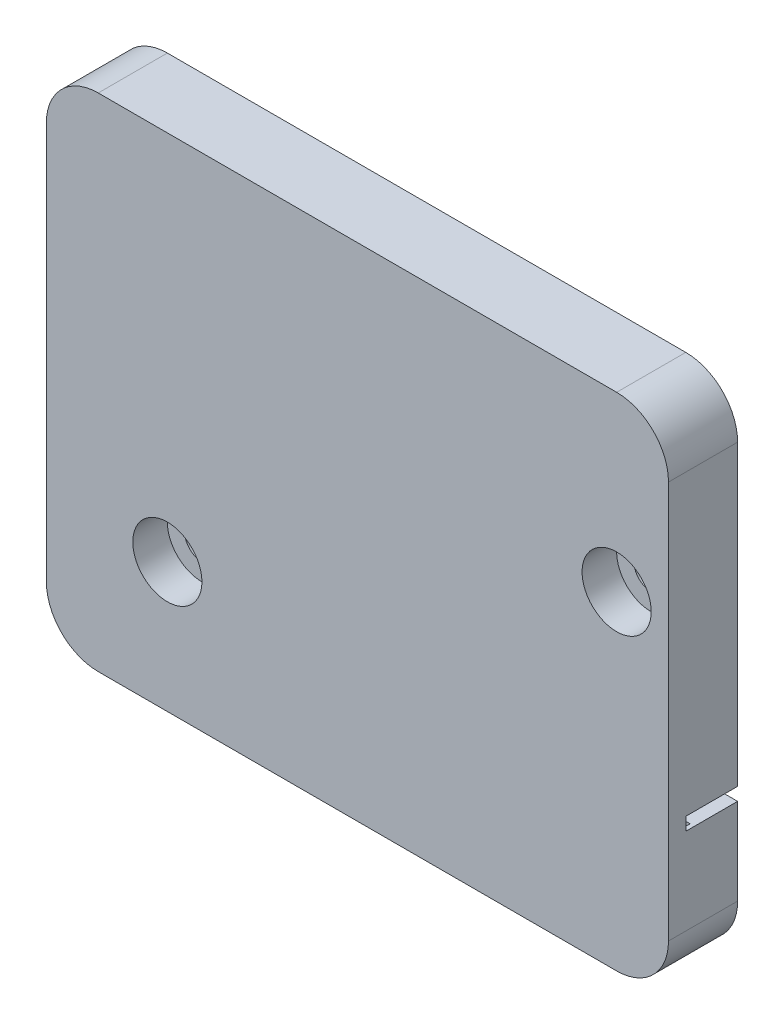
SolidWorks part; units mm, degrees
ref_plane "Front Plane" through (0, 0, 0) normal (0, 0, 1) x (1, 0, 0)
ref_plane "Top Plane" through (0, 0, 0) normal (0, 1, 0) x (1, 0, 0)
ref_plane "Right Plane" through (0, 0, 0) normal (1, 0, 0) x (0, 0, -1)
sketch "Sketch1" plane through (0, 0, 0) normal (0, 0, 1) x (1, 0, 0)
  line L0 (36, 29) -> (-36, -29) construction
  line L1 (-36, -29) -> (36, -29)
  line L2 (-36, -29) -> (-36, 23)
  line L3 (-30, 29) -> (30, 29)
  line L4 (36, -29) -> (36, 23)
  arc A0 (30, 29) -> (36, 23) centre (30, 23) cw
  arc A1 (-36, 23) -> (-30, 29) centre (-30, 23) cw
  dimension "D1" = 6
  dimension "D2" = 72
  dimension "D3" = 58
extrude "Boss-Extrude1" add sketch "Sketch1" along normal blind 8
sketch "Sketch2" plane through (0, 0, 0) normal (0, 0, -1) x (-1, 0, 0)
  line L0 (-33, 0.927) -> (18.4072, 26)
  line L1 (18.4072, 26) -> (30, 26)
  line L2 (33, 23) -> (33, 4.1897)
  line L3 (33, 4.1897) -> (-36, -29.4638)
  line L4 (-33, -9.5) -> (-33, 0.927)
  line L5 (-26.4193, 4.1366) -> (6, 19.9486) construction
  line L6 (36, 5.6529) -> (-15.0217, -19.232) construction
  line L7 (36, 23) -> (36, -29) construction
  line L8 (-30, 29) -> (30, 29) construction
  line L10 (-36, -29) -> (-36, 23) construction
  line L11 (-35, -11.5) -> (-36, -11.5)
  line L12 (-36, -11.5) -> (-36, -29.4638)
  arc A0 (30, 26) -> (33, 23) centre (30, 23) cw
  arc A1 (-35, -11.5) -> (-33, -9.5) centre (-35, -9.5) ccw
  dimension "D3" = 3
  dimension "D6" = 2
  dimension "D1" = 3
  dimension "D2" = 3
  dimension "D4" = 3
  dimension "D5" = 17.9638
extrude "Cut-Extrude1" cut sketch "Sketch2" against normal blind 6
sketch "Sketch3" plane through (0, 0, 8) normal (0, 0, 1) x (1, 0, 0)
  circle A0 centre (-22, -14) radius 2
  circle A1 centre (30, 9) radius 2
  dimension "D1" = 4
extrude "Cut-Extrude2" cut sketch "Sketch3" against normal through all
sketch "Sketch4" plane through (0, 0, 8) normal (0, 0, 1) x (1, 0, 0)
  circle A0 centre (-22, -14) radius 4
  circle A1 centre (30, 9) radius 4
  dimension "D1" = 8
extrude "Cut-Extrude3" cut sketch "Sketch4" against normal blind 4
fillet "Fillet2" radius 6 2 edges at (36, -29, 7) (-36, -29, 4)
fillet "Fillet1" radius 2 1 edges at (33.1796, -28.0882, 3)
sketch "Sketch6" plane through (0, 0, 6) normal (0, 0, -1) x (-1, 0, 0)
  line L0 (-36, -11.5) -> (-36, -23) construction
  line L1 (-26.3861, -29) -> (-30, -29) construction
  line L2 (-36, -13) -> (-36, -23)
  line L3 (-29.3861, -29) -> (-30, -29)
  line L4 (-36, -13) -> (-35.5, -13)
  line L5 (-35.5, -13) -> (-35.5, -23)
  line L6 (-30, -28.5) -> (-29.3861, -28.5)
  line L7 (-29.3861, -28.5) -> (-29.3861, -29)
  line L8 (-31, -4.9122) -> (28.2788, 24)
  line L9 (28.2788, 24) -> (28.498, 23.5506)
  line L10 (28.498, 23.5506) -> (-30.7808, -5.3616)
  line L11 (-30.7808, -5.3616) -> (-31, -4.9122)
  line L12 (-33.5, -13.5025) -> (30.7808, 17.8493)
  line L13 (30.7808, 17.8493) -> (31, 17.3999)
  line L14 (31, 17.3999) -> (-33.2808, -13.9519)
  line L15 (-33.2808, -13.9519) -> (-33.5, -13.5025)
  line L16 (-33.5, -20.8735) -> (30.7808, 10.4783)
  line L17 (30.7808, 10.4783) -> (31, 10.0289)
  line L18 (31, 10.0289) -> (-33.2808, -21.3229)
  line L19 (-33.2808, -21.3229) -> (-33.5, -20.8735)
  line L20 (18.4072, 26) -> (-33, 0.927) construction
  line L23 (30, 26) -> (18.4072, 26) construction
  line L24 (-33, 0.927) -> (-33, -9.5) construction
  line L25 (33, 4.1897) -> (33, 23) construction
  line L26 (33, 4.1897) -> (33, 23) construction
  line L27 (-10.2244, 5.2208) -> (-12.9094, 10.7259) construction
  line L28 (18.4072, 26) -> (-33, 0.927) construction
  line L29 (-8.4412, 5.5341) -> (-5.7562, 0.029) construction
  line L30 (-6.2562, -0.7711) -> (-3.5712, -6.2763) construction
  line L31 (-3.5712, -6.8326) -> (-0.8862, -12.3377) construction
  line L32 (-27.2628, -25.2024) -> (33, 4.1897) construction
  arc A0 (-36, -23) -> (-30, -29) centre (-30, -23) ccw construction
  arc A1 (-36, -23) -> (-30, -29) centre (-30, -23) ccw
  arc A2 (-35.5, -23) -> (-30, -28.5) centre (-30, -23) ccw
  dimension "D1" = 0.5
  dimension "D2" = 1.5
  dimension "D3" = 3
  dimension "D4" = 2
  dimension "D5" = 2
  dimension "D6" = 2
  dimension "D7" = 2
  dimension "D8" = 2
  dimension "D9" = 2
extrude "Boss-Extrude3" add sketch "Sketch6" along normal blind 1
sketch "Sketch7" plane through (0, 0, 5) normal (0, 0, -1) x (-1, 0, 0)
  line L0 (30.7808, 10.4783) -> (-33.5, -20.8735) construction
  line L1 (30.7808, 17.8493) -> (-33.5, -13.5025) construction
  line L2 (28.2788, 24) -> (-31, -4.9122) construction
  line L3 (-36, -13) -> (-36, -23) construction
  line L4 (-30, -29) -> (-29.3861, -29) construction
  line L5 (30.7808, 10.4783) -> (-33.5, -20.8735)
  line L6 (30.7808, 17.8493) -> (-33.5, -13.5025)
  line L7 (28.2788, 24) -> (-31, -4.9122)
  line L8 (-36, -13) -> (-36, -23)
  line L9 (-30, -29) -> (-29.3861, -29)
  line L10 (-31, -4.9122) -> (-30.1233, -6.7098)
  line L11 (-30.1233, -6.7098) -> (29.1555, 22.2024)
  line L12 (29.1555, 22.2024) -> (28.2788, 24)
  line L13 (30.7808, 17.8493) -> (31.6576, 16.0517)
  line L14 (31.6576, 16.0517) -> (-32.6233, -15.3001)
  line L15 (-32.6233, -15.3001) -> (-33.5, -13.5025)
  line L16 (-33.5, -20.8735) -> (-32.6233, -22.6711)
  line L17 (-32.6233, -22.6711) -> (31.6576, 8.6808)
  line L18 (31.6576, 8.6808) -> (30.7808, 10.4783)
  line L19 (-36, -13) -> (-34, -13)
  line L20 (-34, -13) -> (-34, -23)
  line L21 (-30, -27) -> (-29.3861, -27)
  line L22 (-29.3861, -27) -> (-29.3861, -29)
  arc A0 (-36, -23) -> (-30, -29) centre (-30, -23) ccw construction
  arc A1 (-36, -23) -> (-30, -29) centre (-30, -23) ccw
  arc A2 (-34, -23) -> (-30, -27) centre (-30, -23) ccw
  arc A3 (-35.5, -23) -> (-30, -28.5) centre (-30, -23) ccw construction
  dimension "D1" = 2
extrude "Boss-Extrude4" add sketch "Sketch7" along normal up to surface (5 mm away) up to face at (32, 9, 0)
